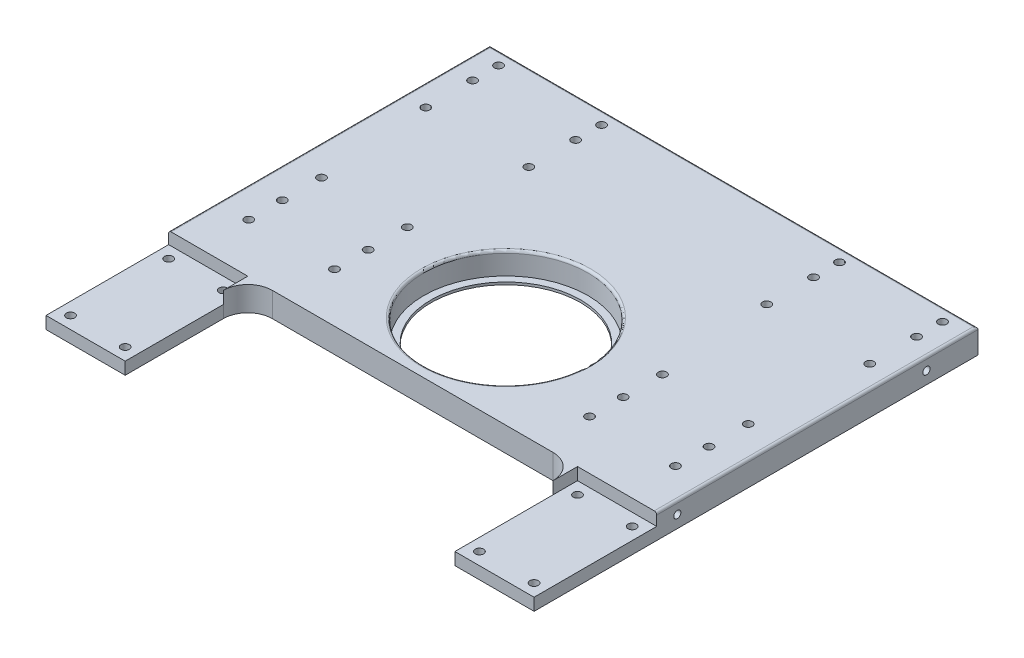
SolidWorks part; units mm, degrees
ref_plane "Ebene vorne" through (0, 0, 0) normal (0, 0, 1) x (1, 0, 0)
ref_plane "Ebene oben" through (0, 0, 0) normal (0, 1, 0) x (1, 0, 0)
ref_plane "Ebene rechts" through (0, 0, 0) normal (1, 0, 0) x (0, 0, -1)
sketch "Skizze1" plane through (0, 0, 0) normal (0, 1, 0) x (1, 0, 0)
  line L1 (-99.5, -210) -> (99.5, -210)
  line L2 (-99.5, -210) -> (-99.5, 210)
  line L3 (-99.5, 210) -> (99.5, 210)
  line L4 (99.5, -210) -> (99.5, 210)
  line L5 (-99.5, -210) -> (99.5, 210) construction
  line L6 (-99.5, 210) -> (99.5, -210) construction
  point P0 (0, 0)
  dimension "D1" = 199
  dimension "D2" = 420
extrude "Aufsatz-Linear austragen1" add sketch "Skizze1" along normal blind 10
ref_plane "Ebene1" through (0, -97.5366, 81.8429) normal (0, -0.766, 0.6428) x (1, 0, 0)
sketch "Skizze2" plane through (0, -97.5366, 81.8429) normal (0, -0.766, 0.6428) x (1, 0, 0)
  line L1 (-99.5, 167.2972) -> (99.5, 167.2972) construction
  circle A0 centre (0, 147.2972) radius 5
  dimension "D1" = 10
  dimension "D2" = 20
extrude "Schnitt-Linear austragen1" [suppressed] cut sketch "Skizze2" against normal blind 30 and the other way blind 10
sketch "Skizze3" [suppressed] plane through (0, -67.9923, 57.0523) normal (0, -0.766, 0.6428) x (1, 0, 0)
  circle A0 centre (0, 101.3345) radius 5
  dimension "D1" = 10
extrude "Aufsatz-Linear austragen2" [suppressed] add sketch "Skizze3" along normal blind 0.1
sketch "Skizze4" plane through (0, -97.5366, 81.8429) normal (0, -0.766, 0.6428) x (1, 0, 0)
  line L0 (0, 167.2972) -> (0, 159.9002) construction
  line L1 (-99.5, 167.2972) -> (99.5, 167.2972) construction
  line L2 (-25, 167.2972) -> (-25, 202.2972)
  line L3 (-25, 202.2972) -> (25, 202.2972)
  line L4 (-25, 167.2972) -> (25, 167.2972)
  line L5 (25, 167.2972) -> (25, 202.2972)
  point P10 (0, 202.2972)
  dimension "D1" = 50
  dimension "D2" = 35
extrude "Aufsatz-Linear austragen3" [suppressed] add sketch "Skizze4" against normal blind 10 separate body
sketch "Skizze5" plane through (0, 10, 0) normal (0, 1, 0) x (1, 0, 0)
  line L0 (0, 0) -> (0, -210) construction
  line L1 (-99.5, -210) -> (99.5, -210) construction
  line L2 (99.5, -210) -> (18, -210)
  line L3 (-18, -210) -> (-99.5, -56)
  line L4 (-99.5, 210) -> (-99.5, -210) construction
  line L5 (-99.5, -56) -> (-99.5, -210)
  line L6 (-99.5, -210) -> (-18, -210)
  line L7 (99.5, -56) -> (99.5, -210)
  line L8 (18, -210) -> (99.5, -56)
  line L9 (-99.5, 210) -> (-99.5, 125)
  line L10 (-99.5, 125) -> (99.5, 125)
  line L11 (99.5, -210) -> (99.5, 210) construction
  line L12 (99.5, 125) -> (99.5, 210)
  line L13 (99.5, 210) -> (-99.5, 210)
  line L14 (67.211, -56) -> (-67.211, -56)
  line L15 (-67.211, -56) -> (-2.6461, -178)
  line L16 (67.211, -56) -> (2.6461, -178)
  line L17 (-2.6461, -178) -> (2.6461, -178)
  line L18 (2.6461, -178) -> (0, -183) construction
  line L19 (-2.6461, -178) -> (0, -183) construction
  point P27 (0, -56)
  dimension "D1" = 36
  dimension "D2" = 154
  dimension "D3" = 85
  dimension "D4" = 32
  dimension "D5" = 27
extrude "Schnitt-Linear austragen2" cut sketch "Skizze5" against normal blind 10
sketch "Skizze6" plane through (0, 10, 0) normal (0, 1, 0) x (1, 0, 0)
  line L0 (0, -210) -> (0, -178) construction
  line L1 (-18, -210) -> (18, -210) construction
  line L2 (-2.6461, -178) -> (2.6461, -178) construction
  line L3 (0, -196.59) -> (-21.075, -196.59) construction
  circle A0 centre (-11, -205) radius 1.7
  circle A1 centre (-11, -188.18) radius 1.7
  circle A2 centre (11, -205) radius 1.7
  circle A3 centre (11, -188.18) radius 1.7
  dimension "D1" = 3.4
  dimension "D2" = 11
  dimension "D3" = 5
  dimension "D4" = 13.41
extrude "Schnitt-Linear austragen3" cut sketch "Skizze6" against normal through all
sketch "Skizze7" plane through (0, 0, 0) normal (0, -1, 0) x (1, 0, 0)
  line L0 (-11, 205) -> (-11, 210) construction
  line L1 (-18, 210) -> (18, 210) construction
  line L2 (-11, 205) -> (-5.1092, 205) construction
  line L3 (-11, 208.4064) -> (-8.05, 206.7032)
  line L4 (-8.05, 206.7032) -> (-8.05, 203.2968)
  line L5 (-11, 201.5936) -> (-8.05, 203.2968)
  line L6 (-11, 201.5936) -> (-13.95, 203.2968)
  line L7 (-13.95, 206.7032) -> (-13.95, 203.2968)
  line L8 (-11, 208.4064) -> (-13.95, 206.7032)
  line L9 (0, 210) -> (0, 121.6034) construction
  line L10 (11, 205) -> (11, 188.18) construction
  line L11 (11, 196.59) -> (0, 196.59) construction
  line L12 (11, 208.4064) -> (8.05, 206.7032)
  line L13 (11, 201.5936) -> (8.05, 203.2968)
  line L14 (8.05, 206.7032) -> (8.05, 203.2968)
  line L15 (11, 201.5936) -> (13.95, 203.2968)
  line L16 (13.95, 206.7032) -> (13.95, 203.2968)
  line L17 (11, 208.4064) -> (13.95, 206.7032)
  line L18 (-8.05, 186.4768) -> (-8.05, 189.8832)
  line L19 (-11, 191.5864) -> (-13.95, 189.8832)
  line L20 (-11, 191.5864) -> (-8.05, 189.8832)
  line L21 (-13.95, 186.4768) -> (-13.95, 189.8832)
  line L22 (-11, 184.7736) -> (-13.95, 186.4768)
  line L23 (-11, 184.7736) -> (-8.05, 186.4768)
  line L24 (8.05, 186.4768) -> (8.05, 189.8832)
  line L25 (11, 191.5864) -> (8.05, 189.8832)
  line L26 (11, 191.5864) -> (13.95, 189.8832)
  line L27 (13.95, 186.4768) -> (13.95, 189.8832)
  line L28 (11, 184.7736) -> (13.95, 186.4768)
  line L29 (11, 184.7736) -> (8.05, 186.4768)
  point P10 (-8.05, 205)
  dimension "D1" = 120
  dimension "D2" = 5.9
extrude "Schnitt-Linear austragen4" cut sketch "Skizze7" against normal blind 4
sketch "Skizze8" plane through (0, 10, 0) normal (0, 1, 0) x (1, 0, 0)
  line L0 (99.5, 115.41) -> (78.872, 115.41) construction
  line L1 (99.5, -56) -> (99.5, 125) construction
  line L2 (-99.5, 125) -> (99.5, 125) construction
  dimension "D1" = 9.59
ref_plane "Ebene2" through (0, 62.6966, -52.6087) normal (0, 0.766, -0.6428) x (-1, 0, 0)
sketch "Skizze9" plane through (0, 62.6966, -52.6087) normal (0, 0.766, -0.6428) x (-1, 0, 0)
  line L0 (-99.5, -81.9813) -> (-78.872, -81.9813) construction
  line L1 (-99.5, 49.3264) -> (-99.5, -89.3277) construction
  line L2 (0, -45.2589) -> (0, -16.2619) construction
  circle A0 centre (-94.5, -81.9813) radius 1.7
  circle A1 centre (94.5, -81.9813) radius 1.7
  circle A2 centre (-30, -81.9813) radius 1.7
  circle A3 centre (30, -81.9813) radius 1.7
  dimension "D1" = 3.4
  dimension "D2" = 5
  dimension "D3" = 30
extrude "Schnitt-Linear austragen5" [suppressed] cut sketch "Skizze9" against normal through all and the other way through all
ref_plane "Ebene3" through (0, 55.0361, -46.1808) normal (0, 0.766, -0.6428) x (-1, 0, 0)
sketch "Skizze10" [suppressed] plane through (0, 55.0361, -46.1808) normal (0, 0.766, -0.6428) x (-1, 0, 0)
  line L0 (-95, -81.9813) -> (-100, -81.9813) construction
  line L1 (-95, -81.9813) -> (-95, -30.0694) construction
  line L2 (-95, -78.7482) -> (-97.8, -80.3647)
  line L3 (-97.8, -80.3647) -> (-97.8, -83.5979)
  line L4 (-95, -85.2145) -> (-97.8, -83.5979)
  line L5 (-95, -85.2145) -> (-92.2, -83.5979)
  line L6 (-92.2, -80.3647) -> (-92.2, -83.5979)
  line L7 (-95, -78.7482) -> (-92.2, -80.3647)
  line L8 (0, 0) -> (0, -45.6283) construction
  line L9 (-30, -81.9813) -> (-95, -81.9813) construction
  line L10 (-62.5, -81.9813) -> (-62.5, -23.1343) construction
  line L11 (-32.8, -80.3647) -> (-32.8, -83.5979)
  line L12 (-30, -85.2145) -> (-32.8, -83.5979)
  line L13 (-30, -85.2145) -> (-27.2, -83.5979)
  line L14 (-27.2, -80.3647) -> (-27.2, -83.5979)
  line L15 (-30, -78.7482) -> (-27.2, -80.3647)
  line L16 (-30, -78.7482) -> (-32.8, -80.3647)
  line L17 (95, -78.7482) -> (92.2, -80.3647)
  line L18 (92.2, -80.3647) -> (92.2, -83.5979)
  line L19 (95, -85.2145) -> (92.2, -83.5979)
  line L20 (95, -85.2145) -> (97.8, -83.5979)
  line L21 (97.8, -80.3647) -> (97.8, -83.5979)
  line L22 (95, -78.7482) -> (97.8, -80.3647)
  line L23 (30, -78.7482) -> (32.8, -80.3647)
  line L24 (30, -78.7482) -> (27.2, -80.3647)
  line L25 (27.2, -80.3647) -> (27.2, -83.5979)
  line L26 (30, -85.2145) -> (27.2, -83.5979)
  line L27 (30, -85.2145) -> (32.8, -83.5979)
  line L28 (32.8, -80.3647) -> (32.8, -83.5979)
  point P9 (-97.8, -81.9813)
  point P31 (97.8, -81.9813)
  dimension "D1" = 120
  dimension "D2" = 5.6
extrude "Schnitt-Linear austragen6" [suppressed] cut sketch "Skizze10" against normal blind 10 and the other way blind 5
sketch "Skizze13" plane through (0, 10, 0) normal (0, 1, 0) x (1, 0, 0)
  line L0 (67.211, -56) -> (99.5, -56) construction
  line L1 (67.211, -56) -> (92.4353, -69.3492) construction
  line L2 (99.5, -56) -> (18, -210) construction
  line L3 (0, 0) -> (0, -38.1435) construction
  line L4 (2.6461, -178) -> (67.211, -56) construction
  line L5 (79.8232, -62.6746) -> (103.8351, -17.3024) construction
  line L6 (99.5, -56) -> (99.5, 125) construction
  line L7 (83.3555, -56) -> (83.3555, -1) construction
  line L8 (93.5, -58.8065) -> (101.0692, -44.504) construction
  line L9 (83.1285, -86.935) -> (57.9043, -73.5858) construction
  line L10 (71.7911, -80.935) -> (86.3039, -80.935) construction
  circle A0 centre (93.5, -58.8065) radius 1.7
  circle A1 centre (72.5142, -58.8065) radius 1.7
  circle A2 centre (81.7891, -80.935) radius 1.7
  circle A3 centre (-81.7891, -80.935) radius 1.7
  circle A4 centre (-93.5, -58.8065) radius 1.7
  circle A5 centre (-72.5142, -58.8065) radius 1.7
  dimension "D1" = 6
  dimension "D5" = 35
  dimension "D3" = 3.4
  dimension "D6" = 3.4
  dimension "D2" = 6
  dimension "D4" = 6
extrude "Schnitt-Linear austragen7" [suppressed] cut sketch "Skizze13" against normal through all
sketch "Skizze14" plane through (100.8819, 0, 53.3888) normal (0.8839, 0, 0.4678) x (0.4678, 0, -0.8839)
  line L0 (-37.9543, 5) -> (-37.9543, 10)
  line L5 (-2.9543, 0) -> (-2.9543, 10) construction
  line L6 (-37.9543, 5) -> (-2.9543, 5)
  line L7 (-2.9543, 10) -> (-177.1905, 10) construction
  line L8 (-37.9543, 10) -> (-2.9543, 10)
  line L9 (-2.9543, 10) -> (-2.9543, 5)
  dimension "D1" = 35
extrude "Schnitt-Linear austragen8" [suppressed] cut sketch "Skizze14" against normal up to surface (28.9525 mm away)
mirror "Spiegeln1" [suppressed] about plane through (0, 0, 0) normal (1, 0, 0)
sketch "Skizze15" [suppressed] plane through (95, 0, 0) normal (1, 0, 0) x (0, 0, -1)
  line L0 (4, 10) -> (4, 0)
  line L1 (4, 0) -> (65, 0)
  line L2 (65, 0) -> (65, 10)
  line L3 (65, 10) -> (4, 10)
extrude "Schnitt-Linear austragen9" [suppressed] cut sketch "Skizze15" against normal through all
sketch "Skizze16" plane through (0, 0, 0) normal (0, -1, 0) x (1, 0, 0)
  line L0 (0, 210) -> (0, 178) construction
  line L1 (-18, 210) -> (18, 210) construction
  line L2 (-2.6461, 178) -> (2.6461, 178) construction
  line L3 (11, 196.59) -> (0, 196.59) construction
  line L4 (11, 205) -> (11, 188.18) construction
  line L6 (-17.5, 193.09) -> (17.5, 193.09)
  line L7 (-17.5, 193.09) -> (-17.5, 200.09)
  line L8 (-17.5, 200.09) -> (17.5, 200.09)
  line L9 (17.5, 193.09) -> (17.5, 200.09)
  line L10 (-17.5, 193.09) -> (17.5, 200.09) construction
  line L11 (-17.5, 200.09) -> (17.5, 193.09) construction
  dimension "D1" = 7
  dimension "D2" = 35
extrude "Schnitt-Linear austragen10" cut sketch "Skizze16" against normal blind 5
sketch "Skizze17" plane through (17.5, 0, 0) normal (-1, 0, 0) x (0, 0, 1)
  line L0 (196.59, 0) -> (196.59, 11.1261) construction
  line L1 (193.09, 0) -> (200.09, 0) construction
  line L2 (193.09, 5) -> (196.59, 8.5)
  line L3 (196.59, 8.5) -> (200.09, 5)
  line L4 (200.09, 5) -> (193.09, 5)
  dimension "D1" = 90
extrude "Schnitt-Linear austragen11" cut sketch "Skizze17" along normal up to surface (35 mm away) up to face at (-17.5, 2.5, 196.59)
sketch "Skizze18" [suppressed] plane through (0, 10, 0) normal (0, 1, 0) x (1, 0, 0)
  line L0 (0, -210) -> (0, 0) construction
  line L1 (-18, -210) -> (18, -210) construction
  line L2 (62.5765, -72.2325) -> (35.4483, -67.5372)
  line L3 (15.3378, -155.8503) -> (-22.1774, -134.6566)
  line L4 (2.8247, -178) -> (62.5765, -72.2325) construction
  line L5 (-15.3378, -155.8503) -> (22.1774, -134.6566)
  line L6 (58.6594, -79.166) -> (40.7308, -76.063)
  line L7 (0, -147.1854) -> (19.5429, -147.1854) construction
  line L8 (0, -95.4) -> (31.4297, -95.4) construction
  line L9 (11.6488, -162.3803) -> (0, -155.7995)
  line L10 (-71.7468, -56) -> (-2.8247, -178) construction
  line L11 (0, -95.4) -> (-37.5153, -116.5937) construction
  line L12 (-37.5153, -116.5937) -> (-39.2566, -117.5774) construction
  line L13 (-11.6488, -162.3803) -> (0, -155.7995)
  line L14 (-58.6594, -79.166) -> (-40.7308, -76.063)
  line L15 (-62.5765, -72.2325) -> (-35.4483, -67.5372)
  circle A0 centre (0, -95.4) radius 33.5
  arc A1 (7.4594, -151.3994) -> (7.4594, -142.9713) centre (9.84, -147.1854) cw
  arc A2 (-7.4594, -151.3994) -> (-7.4594, -142.9713) centre (-9.84, -147.1854) ccw
  circle A3 centre (0, -95.4) radius 45.0879
  point P17 (0, -147.1854)
  point P36 (5, -147.1854)
  point P40 (-5, -147.1854)
  line M16 (62.5765, -72.2325) -> (2.8247, -178)
  line M18 (-2.8247, -178) -> (-71.7468, -56)
  dimension "D2" = 67
  dimension "D5" = 2
  dimension "D4" = 10
  dimension "D1" = 114.6
  dimension "D3" = 7.5
  dimension "D6" = 7.5
extrude "Aufsatz-Linear austragen4" [suppressed] add sketch "Skizze18" against normal blind 10 contours A3 L15 L14 M18 | A3 A0 M16 M18 | A3 L6 L2 M16 | A2 L5 L3 | A3 L3 L5 | L3 A1 L5 | L13 L9 L3 L5 M18 M16
sketch "Skizze19" [suppressed] plane through (0, 0, 0) normal (0, -1, 0) x (1, 0, 0)
  circle A0 centre (0, 35.4) radius 31.5
  circle A1 centre (0, 35.4) radius 33.5
  circle A2 centre (0, 35.4) radius 33.5 construction
  dimension "D1" = 63
extrude "Aufsatz-Linear austragen5" [suppressed] add sketch "Skizze19" against normal blind 1
sketch "Skizze20" plane through (0, 10, 0) normal (0, 1, 0) x (1, 0, 0)
  line L0 (99.5, 119.52) -> (55.4083, 119.52) construction
  line L1 (99.5, -56) -> (99.5, 125) construction
  line L2 (-99.5, 125) -> (99.5, 125) construction
  line L3 (0, 125) -> (0, 96.9732) construction
  line L4 (87, 43.82) -> (52, 43.82) construction
  line L5 (90.5, 119.52) -> (90.5, 16.5236) construction
  line L6 (87, 43.82) -> (87, -19.0314) construction
  line L7 (69.5, 43.82) -> (69.5, 8.7303) construction
  circle A0 centre (90.5, 119.52) radius 1.7
  circle A1 centre (48.5, 119.52) radius 1.7
  circle A2 centre (-48.5, 119.52) radius 1.7
  circle A3 centre (-90.5, 119.52) radius 1.7
  circle A4 centre (87, 43.82) radius 1.7
  circle A5 centre (52, 43.82) radius 1.7
  circle A6 centre (-87, 43.82) radius 1.7
  circle A7 centre (-52, 43.82) radius 1.7
  circle A8 centre (90.5, 108.94) radius 1.7
  circle A9 centre (87, 27.84) radius 1.7
  circle A10 centre (48.5, 108.94) radius 1.7
  circle A11 centre (52, 27.84) radius 1.7
  circle A12 centre (-48.5, 108.94) radius 1.7
  circle A13 centre (-90.5, 108.94) radius 1.7
  circle A14 centre (-52, 27.84) radius 1.7
  circle A15 centre (-87, 27.84) radius 1.7
  circle A16 centre (90.5, 89.84) radius 1.7
  circle A17 centre (87, 14.13) radius 1.7
  circle A18 centre (52, 14.13) radius 1.7
  circle A19 centre (48.5, 89.84) radius 1.7
  circle A20 centre (-90.5, 89.84) radius 1.7
  circle A21 centre (-48.5, 89.84) radius 1.7
  circle A22 centre (-52, 14.13) radius 1.7
  circle A23 centre (-87, 14.13) radius 1.7
  dimension "D1" = 3.4
  dimension "D2" = 5.48
  dimension "D3" = 9
  dimension "D4" = 42
  dimension "D5" = 75.7
  dimension "D6" = 12.5
  dimension "D7" = 35
  dimension "D8" = 10.58
  dimension "D9" = 15.98
  dimension "D10" = 19.1
  dimension "D11" = 13.71
extrude "Schnitt-Linear austragen12" cut sketch "Skizze20" against normal through all
sketch "Skizze21" plane through (0, 10, 0) normal (0, 1, 0) x (1, 0, 0)
  line L0 (-67.211, -56) -> (-67.211, -6)
  line L1 (-67.211, -6) -> (67.211, -6)
  line L2 (67.211, -6) -> (67.211, -56)
  line L3 (67.211, -56) -> (-67.211, -56) construction
  line L4 (-67.211, -56) -> (67.211, -56)
  dimension "D1" = 50
extrude "Schnitt-Linear austragen13" cut sketch "Skizze21" against normal through all
sketch "Skizze22" plane through (0, 10, 0) normal (0, 1, 0) x (1, 0, 0)
  line L0 (-67.211, -56) -> (-2.6461, -178)
  arc A0 (-67.211, -56) -> (-2.6461, -178) centre (60.0769, -66.7211) ccw
  line M19 (-2.6461, -178) -> (-67.211, -56)
extrude "Schnitt-Linear austragen14" cut sketch "Skizze22" against normal through all contours M19 region at (-42.1385, 10, 120.8156)
sketch "Skizze23" plane through (0, 10, 0) normal (0, 1, 0) x (1, 0, 0)
  line L0 (-18, -210) -> (-99.5, -56) construction
  line L1 (-99.5, -56) -> (-18, -210)
  arc A0 (-18, -210) -> (-99.5, -56) centre (114.4449, -41.3416) cw
  arc A2 (-67.211, -56) -> (-2.6461, -178) centre (60.0769, -66.7211) ccw construction
  dimension "D1" = 60
extrude "Aufsatz-Linear austragen6" add sketch "Skizze23" against normal blind 10
mirror "Spiegeln2" about plane through (0, 0, 0) normal (1, 0, 0) of "Aufsatz-Linear austragen6", "Schnitt-Linear austragen14"
sketch "Skizze25" plane through (0, 10, 0) normal (0, 1, 0) x (1, 0, 0)
  line L0 (-99.5, -56) -> (-67.211, -56) construction
  line L1 (-99.5, -6) -> (-99.5, -56) construction
  line L2 (-99.5, -6) -> (-67.211, -6) construction
  line L3 (-67.211, -6) -> (-67.211, -56) construction
  line L4 (-83.3555, -6) -> (-83.3555, -56) construction
  line L5 (-99.5, -31) -> (-67.211, -31) construction
  line L6 (-99.5, 125) -> (-99.5, -56) construction
  circle A0 centre (-94.5, -11) radius 1.7
  circle A1 centre (-72.211, -11) radius 1.7
  circle A2 centre (-72.211, -51) radius 1.7
  circle A3 centre (-94.5, -51) radius 1.7
  dimension "D2" = 3.4
  dimension "D1" = 50
  dimension "D3" = 5
  dimension "D4" = 5
extrude "Schnitt-Linear austragen15" cut sketch "Skizze25" against normal through all
sketch "Skizze26" plane through (-99.5, 0, 0) normal (-1, 0, 0) x (0, 0, 1)
  line L0 (6, 5) -> (6, 13.1015)
  line L1 (56, 0) -> (56, 10) construction
  line L2 (56, 5) -> (6, 5)
  line L4 (-125, 0) -> (56, 0) construction
  line L5 (56, 5) -> (56, 0)
  line L6 (6, 13.1015) -> (200.6846, 82.5463)
  line L7 (200.6846, 82.5463) -> (242.9972, -41.0376)
  line L8 (242.9972, -41.0376) -> (91.2415, -60.2848)
  line L9 (91.2415, -60.2848) -> (56, 0)
  dimension "D1" = 50
mirror "Spiegeln3" about plane through (0, 0, 0) normal (1, 0, 0) of "Schnitt-Linear austragen15"
extrude "Schnitt-Linear austragen16" cut sketch "Skizze26" against normal through all
sketch "Skizze27" plane through (0, 10, 0) normal (0, 1, 0) x (1, 0, 0)
  line L0 (0, -6) -> (0, 125) construction
  line L1 (99.5, -6) -> (-99.5, -6) construction
  line L2 (-99.5, 125) -> (99.5, 125) construction
  line L3 (99.5, -6) -> (-99.5, -6) construction
  circle A0 centre (0, 32) radius 33.5
  dimension "D1" = 67
  dimension "D2" = 38
extrude "Schnitt-Linear austragen17" cut sketch "Skizze27" against normal through all
sketch "Skizze28" plane through (0, 0, 0) normal (0, -1, 0) x (1, 0, 0)
  circle A0 centre (0, -32) radius 30.5
  circle A1 centre (0, -32) radius 33.5 construction
  circle A2 centre (0, -32) radius 36.0063
  dimension "D1" = 3
extrude "Aufsatz-Linear austragen7" add sketch "Skizze28" against normal blind 1
sketch "Skizze29" plane through (-99.5, 0, 0) normal (-1, 0, 0) x (0, 0, 1)
  line L0 (-125, 5) -> (-93.4233, 5) construction
  line L1 (-125, 0) -> (-125, 10) construction
  circle A0 centre (-104, 5) radius 1.5
  circle A1 centre (-2.4, 5) radius 1.45
  dimension "D1" = 3
  dimension "D3" = 2.9
  dimension "D2" = 21
extrude "Schnitt-Linear austragen18" cut sketch "Skizze29" against normal blind 10
sketch "Skizze30" plane through (0, 0, -125) normal (0, 0, -1) x (-1, 0, 0)
  line L0 (99.5, 5) -> (60.2539, 5) construction
  line L1 (99.5, 0) -> (99.5, 10) construction
  line L2 (0, 0) -> (0, 19.3538) construction
  line L3 (99.5, 0) -> (-99.5, 0) construction
  circle A0 centre (94.5, 5) radius 1.45
  circle A1 centre (78.5, 5) radius 1.45
  dimension "D1" = 2.9
  dimension "D2" = 5
  dimension "D3" = 21
extrude "Schnitt-Linear austragen19" cut sketch "Skizze30" against normal blind 10
mirror "Spiegeln4" about plane through (0, 0, 0) normal (1, 0, 0) of "Schnitt-Linear austragen18", "Schnitt-Linear austragen19"
sketch "Skizze31" plane through (0, 0, 0) normal (0, -1, 0) x (1, 0, 0)
  line L0 (0, -125) -> (0, -73.0202) construction
  line L1 (-99.5, -125) -> (99.5, -125) construction
  circle A0 centre (-90.5, -119.52) radius 2.95
  circle A1 centre (-48.5, -119.52) radius 2.95
  circle A2 centre (-87, -43.82) radius 2.95
  circle A3 centre (-52, -43.82) radius 2.95
  circle A4 centre (52, -43.82) radius 2.95
  circle A5 centre (87, -43.82) radius 2.95
  circle A6 centre (48.5, -119.52) radius 2.95
  circle A7 centre (90.5, -119.52) radius 2.95
  circle A8 centre (-90.5, -108.94) radius 2.95
  circle A9 centre (-90.5, -89.84) radius 2.95
  circle A10 centre (-48.5, -89.84) radius 2.95
  circle A11 centre (-48.5, -108.94) radius 2.95
  circle A12 centre (-87, -14.13) radius 2.95
  circle A13 centre (-87, -27.84) radius 2.95
  circle A14 centre (-52, -27.84) radius 2.95
  circle A15 centre (-52, -14.13) radius 2.95
  circle A16 centre (48.5, -108.94) radius 2.95
  circle A17 centre (48.5, -89.84) radius 2.95
  circle A18 centre (90.5, -89.84) radius 2.95
  circle A19 centre (90.5, -108.94) radius 2.95
  circle A20 centre (52, -14.13) radius 2.95
  circle A21 centre (52, -27.84) radius 2.95
  circle A22 centre (87, -27.84) radius 2.95
  circle A23 centre (87, -14.13) radius 2.95
  dimension "D1" = 5.9
extrude "Schnitt-Linear austragen20" cut sketch "Skizze31" against normal blind 3.5
move or copy body "Körper-Verschieben/Kopieren1" [suppressed] bodies to move or copy 132 copy no rotation origin (0, 5, -34.5) rotation axis (1, 0, 0) rotation angle 90
sketch "Skizze32" plane through (0, 10, 0) normal (0, 1, 0) x (1, 0, 0)
  line L1 (25.1613, 106.641) -> (-1.8387, 106.641)
  line L2 (25.1613, 106.641) -> (25.1613, 77.141)
  line L3 (25.1613, 77.141) -> (-1.8387, 77.141)
  line L4 (-1.8387, 106.641) -> (-1.8387, 77.141)
  line L5 (25.1613, 106.641) -> (-1.8387, 77.141) construction
  line L6 (25.1613, 77.141) -> (-1.8387, 106.641) construction
  circle A0 centre (25.1613, 77.141) radius 1.45
  circle A1 centre (-1.8387, 77.141) radius 1.45
  circle A2 centre (-1.8387, 106.641) radius 1.45
  circle A3 centre (25.1613, 106.641) radius 1.45
  point P0 (11.6613, 91.891)
  dimension "D3" = 2.9
  dimension "D1" = 29.5
  dimension "D2" = 27
extrude "Schnitt-Linear austragen21" [suppressed] cut sketch "Skizze32" against normal through all contours L3 A0 L2 | L2 A0 L3 | L4 A1 L3 | L3 A1 L4 | L1 A2 L4 | L4 A2 L1 | L2 A3 L1 | L1 A3 L2
fillet "Verrundung1" radius 10 2 edges at (-67.211, 2.5, 6) (67.211, 2.5, 6)
sketch "Skizze33" plane through (0, 5, 0) normal (0, 1, 0) x (1, 0, 0)
  line L0 (-67.211, -16) -> (-67.211, -6)
  line L1 (-57.211, -6) -> (-99.5, -6) construction
  line L2 (-67.211, -6) -> (-57.211, -6)
  line L3 (99.5, -6) -> (-99.5, -6) construction
  line L4 (0, -6) -> (0, -39.688) construction
  line L5 (67.211, -6) -> (57.211, -6)
  line L6 (67.211, -16) -> (67.211, -6)
  arc A0 (-57.211, -6) -> (-67.211, -16) centre (-57.211, -16) ccw construction
  arc A1 (-67.211, -16) -> (-57.211, -6) centre (-57.211, -16) cw
  arc A2 (67.211, -16) -> (57.211, -6) centre (57.211, -16) ccw
extrude "Aufsatz-Linear austragen8" add sketch "Skizze33" along normal up to surface (5 mm away) up to face at (0, 10, 1.5)
fillet "Verrundung2" radius 1 4 edges at (0, 10, 1.5) (99.5, 10, -59.5) (0, 10, -125) (-99.5, 10, -59.5)
sketch "Skizze34" plane through (0, 10, 0) normal (0, 1, 0) x (1, 0, 0)
  line L0 (50.1242, 120.022) -> (-50.1242, 120.022) construction
  circle A0 centre (-48.5, 119.52) radius 1.7 construction
  circle A1 centre (48.5, 119.52) radius 1.7 construction
  text T0 "OpenAstroTech" font "@Adobe Heiti Std R" height in points 22
extrude "Schnitt-Linear austragen22" [suppressed] cut sketch "Skizze34" against normal blind 0.8
sketch "Skizze35" plane through (0, 10, 0) normal (0, 1, 0) x (1, 0, 0)
  line L0 (0, 124) -> (0, 69.8916) construction
  line L1 (98.5, 124) -> (-98.5, 124) construction
  circle A0 centre (26.9, 117.4942) radius 1.45
  circle A1 centre (26.9, 86.4942) radius 1.45
  circle A2 centre (-26.9, 86.4942) radius 1.45
  circle A3 centre (-26.9, 117.4942) radius 1.45
  dimension "D1" = 2.9
  dimension "D2" = 53.8
  dimension "D3" = 31
extrude "Schnitt-Linear austragen23" [suppressed] cut sketch "Skizze35" against normal blind 10
chamfer "Fase1" distance 0.62 angle 45 47 edges at (-90.5, 3.5, -91.54) (-90.5, 3.5, -92.79) (-90.5, 3.5, -110.64) (-90.5, 3.5, -111.89) (-90.5, 3.5, -121.22) (-90.5, 3.5, -122.47) (-87, 3.5, -45.52) (-87, 3.5, -46.77) (-87, 3.5, -29.54) (-87, 3.5, -30.79) (-87, 3.5, -15.83) (-87, 3.5, -17.08) (-52, 3.5, -15.83) (-52, 3.5, -17.08) (-52, 3.5, -29.54) (-52, 3.5, -30.79) (-52, 3.5, -45.52) (-52, 3.5, -46.77) (-48.5, 3.5, -91.54) (-48.5, 3.5, -92.79) (-48.5, 3.5, -110.64) (-48.5, 3.5, -111.89) (52, 3.5, -12.43) (52, 3.5, -11.18) (52, 3.5, -26.14) (52, 3.5, -24.89) (52, 3.5, -42.12) (52, 3.5, -40.87) (48.5, 3.5, -88.14) (48.5, 3.5, -86.89) (48.5, 3.5, -107.24) (48.5, 3.5, -105.99) (48.5, 3.5, -117.82) (48.5, 3.5, -116.57) (90.5, 3.5, -117.82) (90.5, 3.5, -116.57) (90.5, 3.5, -107.24) (90.5, 3.5, -105.99) (-48.5, 3.5, -122.47) (90.5, 3.5, -88.14) (90.5, 3.5, -86.89) (87, 3.5, -42.12) (87, 3.5, -40.87) (87, 3.5, -26.14) (87, 3.5, -24.89) (87, 3.5, -12.43) (87, 3.5, -11.18)
sketch "Skizze36" plane through (0, 10, 0) normal (0, 1, 0) x (1, 0, 0)
  line L0 (-117.051, 68.7567) -> (-66.9468, 68.7567)
  line L1 (-66.9468, 68.7567) -> (-66.9468, 137.1475)
  line L2 (-66.9468, 137.1475) -> (152.3569, 201.2504)
  line L3 (152.3569, 201.2504) -> (200.3815, -97.7642)
  line L4 (200.3815, -97.7642) -> (-142.4512, -123.0035)
  line L5 (-142.4512, -123.0035) -> (-163.1334, 56.1249)
  line L6 (-163.1334, 56.1249) -> (-117.051, 68.7567)
extrude "Schnitt-Linear austragen24" [suppressed] cut sketch "Skizze36" against normal through all
